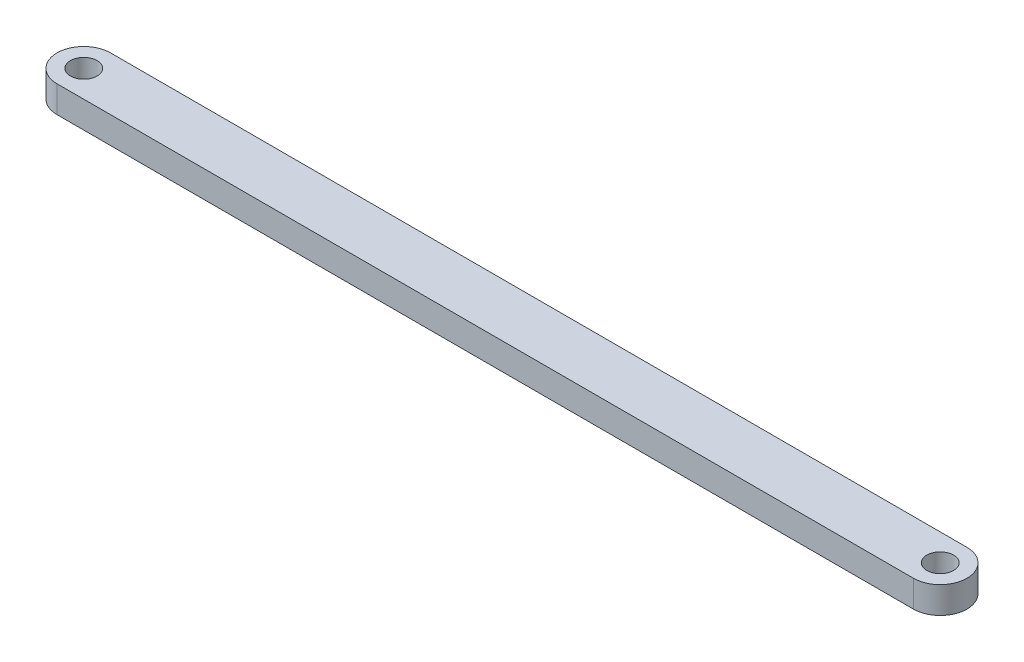
SolidWorks part; units mm, degrees
ref_plane "Front Plane" through (0, 0, 0) normal (0, 0, 1) x (1, 0, 0)
ref_plane "Top Plane" through (0, 0, 0) normal (0, 1, 0) x (1, 0, 0)
ref_plane "Right Plane" through (0, 0, 0) normal (1, 0, 0) x (0, 0, -1)
sketch "Sketch2" plane through (0, 0, 0) normal (0, 1, 0) x (1, 0, 0)
  line L0 (80, 0) -> (-80, 0) construction
  line L1 (80, -5) -> (-80, -5)
  line L2 (80, 5) -> (-80, 5)
  arc A0 (80, -5) -> (80, 5) centre (80, 0) ccw
  arc A1 (-80, 5) -> (-80, -5) centre (-80, 0) ccw
  circle A2 centre (80, 0) radius 2.5
  circle A3 centre (-80, 0) radius 2.5
  point P3 (0, 0)
  dimension "D2" = 5
  dimension "D3" = 5
  dimension "D1" = 160
extrude "Boss-Extrude1" add sketch "Sketch2" along normal blind 5
